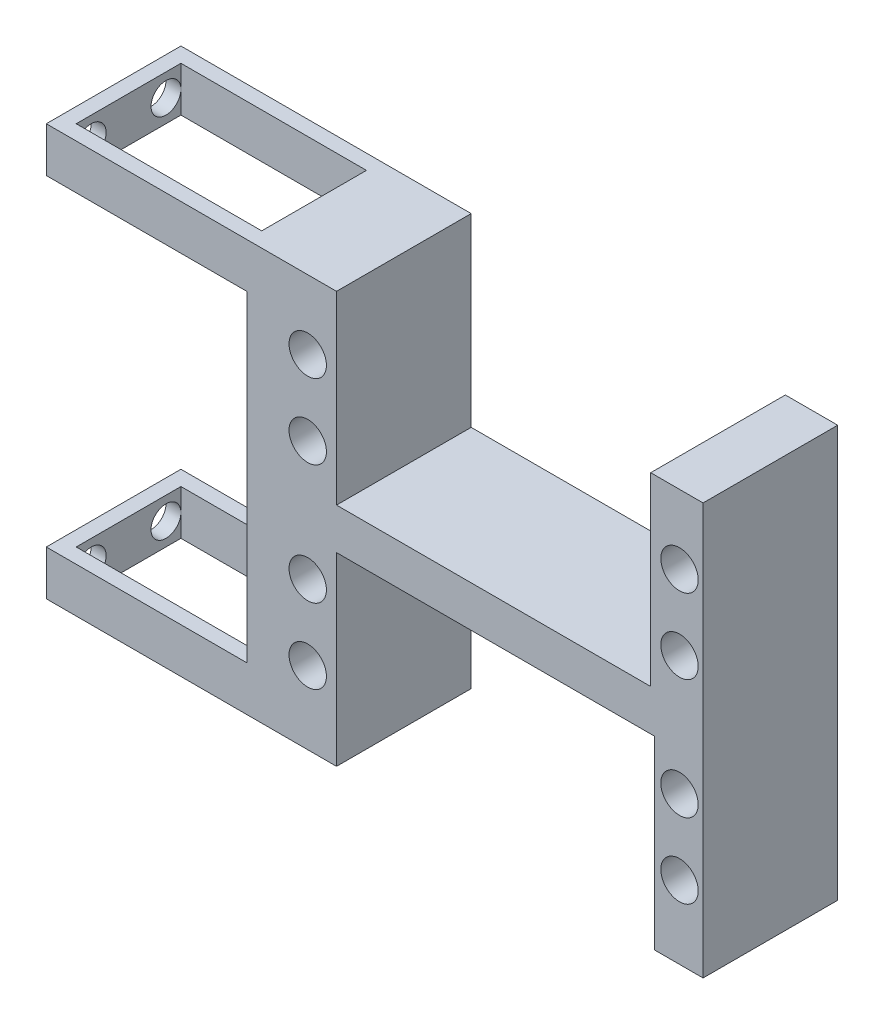
SolidWorks part; units mm, degrees
ref_plane "Front Plane" through (0, 0, 0) normal (0, 0, 1) x (1, 0, 0)
ref_plane "Top Plane" through (0, 0, 0) normal (0, 1, 0) x (1, 0, 0)
ref_plane "Right Plane" through (0, 0, 0) normal (1, 0, 0) x (0, 0, -1)
sketch "Sketch2" plane through (0, 0, 0) normal (0, 0, 1) x (1, 0, 0)
  line L0 (0, -55) -> (0, 55) construction
  line L1 (0, 55) -> (61, 55)
  line L2 (0, 55) -> (0, 0)
  line L3 (0, 0) -> (61, 0)
  line L4 (61, 55) -> (61, 0)
  line L5 (55, 0) -> (-55, 0) construction
  line L7 (12, 50.75) -> (54, 50.75)
  line L8 (12, 50.75) -> (12, 30.25)
  line L9 (12, 30.25) -> (54, 30.25)
  line L10 (54, 50.75) -> (54, 30.25)
  line L11 (12, 24.75) -> (54.5, 24.75)
  line L12 (12, 24.75) -> (12, 4.25)
  line L13 (12, 4.25) -> (54.5, 4.25)
  line L14 (54.5, 24.75) -> (54.5, 4.25)
  dimension "D1" = 55
  dimension "D2" = 7
  dimension "D3" = 42
  dimension "D4" = 20.5
  dimension "D5" = 5.5
  dimension "D6" = 42.5
  dimension "D7" = 20.5
  dimension "D8" = 12
  dimension "D9" = 4.25
  dimension "D10" = 12
extrude "Boss-Extrude1" add sketch "Sketch2" along normal blind 18
sketch "Sketch3" plane through (0, 0, 18) normal (0, 0, 1) x (1, 0, 0)
  line L0 (54, 50.75) -> (12, 50.75) construction
  line L1 (12, 50.75) -> (12, 30.25) construction
  line L2 (12, 24.75) -> (12, 4.25) construction
  line L3 (54.5, 24.75) -> (12, 24.75) construction
  circle A0 centre (8.15, 45.75) radius 2.5
  circle A1 centre (8.15, 35.75) radius 2.5
  circle A6 centre (57.85, 35.75) radius 2.5
  circle A7 centre (57.85, 45.75) radius 2.5
  circle A8 centre (8.15, 19.75) radius 2.5
  circle A9 centre (8.15, 9.75) radius 2.5
  circle A10 centre (57.85, 9.75) radius 2.5
  circle A11 centre (57.85, 19.75) radius 2.5
  dimension "D1" = 10
  dimension "D2" = 5
  dimension "D3" = 5
  dimension "D4" = 5
  dimension "D5" = 3.85
  dimension "D6" = 3.85
  dimension "D7" = 45.85
  dimension "D8" = 45.85
  dimension "D9" = 45.85
  dimension "D10" = 45.85
  dimension "D11" = 5
  dimension "D12" = 5
  dimension "D13" = 3.85
  dimension "D14" = 3.85
  dimension "D15" = 10
  dimension "D16" = 5
  dimension "D17" = 5
  dimension "D18" = 5
  dimension "D19" = 5
  dimension "D20" = 5
  dimension "D21" = 5
  dimension "D22" = 5
  dimension "D23" = 10
  dimension "D24" = 10
extrude "Cut-Extrude1" cut sketch "Sketch3" against normal blind 10
sketch "Sketch5" plane through (0, 0, 0) normal (-1, 0, 0) x (0, 0, 1)
  line L0 (0, -55) -> (0, 55) construction
  line L1 (0, 55) -> (2, 55)
  line L2 (0, 55) -> (0, 49)
  line L3 (0, 49) -> (2, 49)
  line L4 (2, 55) -> (2, 49)
  line L5 (18, 55) -> (0, 55) construction
  line L6 (55, 0) -> (-55, 0) construction
  line L7 (18, 55) -> (16, 55)
  line L8 (18, 55) -> (18, 49)
  line L9 (18, 49) -> (16, 49)
  line L10 (16, 55) -> (16, 49)
  line L11 (0, 0) -> (2, 0)
  line L12 (0, 0) -> (0, 6)
  line L13 (0, 6) -> (2, 6)
  line L14 (2, 0) -> (2, 6)
  line L15 (18, 0) -> (16, 0)
  line L16 (18, 0) -> (18, 6)
  line L17 (18, 6) -> (16, 6)
  line L18 (16, 0) -> (16, 6)
  line L19 (18, 55) -> (18, 0) construction
  dimension "D1" = 2
  dimension "D2" = 2
  dimension "D3" = 6
  dimension "D4" = 6
  dimension "D5" = 2
  dimension "D6" = 2
  dimension "D7" = 6
  dimension "D8" = 6
extrude "Boss-Extrude2" add sketch "Sketch5" along normal blind 26.8
sketch "Sketch6" plane through (0, 0, 2) normal (0, 0, 1) x (1, 0, 0)
  line L0 (-26.8, 49) -> (0, 49) construction
  line L1 (-24.8, 49) -> (-26.8, 49)
  line L2 (-24.8, 49) -> (-24.8, 55)
  line L3 (-24.8, 55) -> (-26.8, 55)
  line L4 (-26.8, 49) -> (-26.8, 55)
  line L5 (61, 55) -> (-26.8, 55) construction
  line L6 (-26.8, 55) -> (-26.8, 49) construction
  line L7 (55, 0) -> (-55, 0) construction
  line L8 (-26.8, 6) -> (-24.8, 6)
  line L9 (-26.8, 6) -> (-26.8, 0)
  line L10 (-26.8, 0) -> (-24.8, 0)
  line L11 (-24.8, 6) -> (-24.8, 0)
  dimension "D1" = 2
  dimension "D2" = 2
extrude "Boss-Extrude3" add sketch "Sketch6" along normal up to next
sketch "Sketch7" plane through (-26.8, 0, 0) normal (-1, 0, 0) x (0, 0, 1)
  line L0 (0, -55) -> (0, 55) construction
  line L1 (18, 55) -> (0, 55) construction
  line L2 (18, 49) -> (18, 55) construction
  line L3 (18, 0) -> (18, 6) construction
  line L4 (18, 6) -> (0, 6) construction
  circle A0 centre (4, 52) radius 2
  circle A1 centre (14, 52) radius 2
  circle A2 centre (4, 3) radius 2
  circle A3 centre (14, 3) radius 2
  dimension "D1" = 4
  dimension "D2" = 4
  dimension "D3" = 4
  dimension "D4" = 3
  dimension "D5" = 4
  dimension "D6" = 3
  dimension "D7" = 4
  dimension "D8" = 4
  dimension "D9" = 4
  dimension "D10" = 4
  dimension "D11" = 3
  dimension "D12" = 3
extrude "Cut-Extrude2" cut sketch "Sketch7" against normal blind 10
sketch "Sketch8" plane through (0, 0, 18) normal (0, 0, 1) x (1, 0, 0)
  line L0 (61, 55) -> (-26.8, 55) construction
  line L1 (12, 50.75) -> (54, 50.75)
  line L2 (12, 50.75) -> (12, 55)
  line L3 (12, 55) -> (54, 55)
  line L4 (54, 50.75) -> (54, 55)
  line L5 (9.9, 0) -> (-9.9, 0) construction
  line L6 (12, 4.25) -> (54.5, 4.25)
  line L7 (12, 4.25) -> (12, 0)
  line L8 (12, 0) -> (54.5, 0)
  line L9 (54.5, 4.25) -> (54.5, 0)
extrude "Cut-Extrude3" cut sketch "Sketch8" against normal up to next
